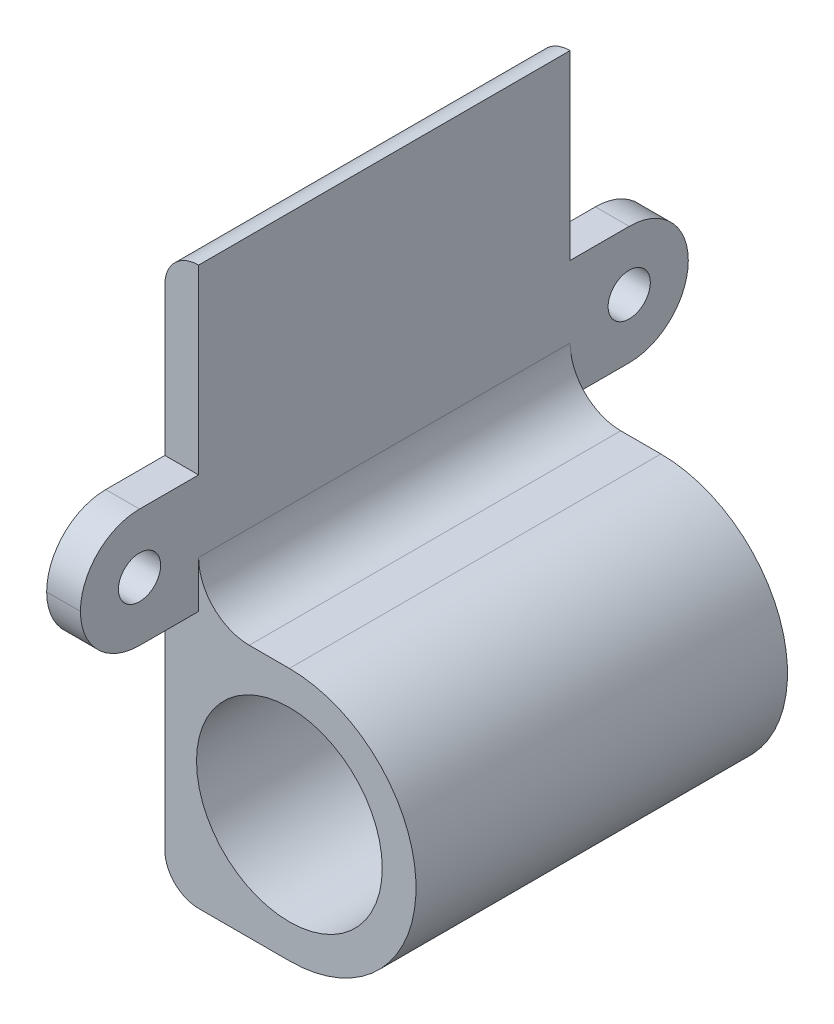
SolidWorks part; units mm, degrees
ref_plane "Front Plane" through (0, 0, 0) normal (0, 0, 1) x (1, 0, 0)
ref_plane "Top Plane" through (0, 0, 0) normal (0, 1, 0) x (1, 0, 0)
ref_plane "Right Plane" through (0, 0, 0) normal (1, 0, 0) x (0, 0, -1)
sketch "Sketch2" plane through (0, 0, 0) normal (0, 0, 1) x (1, 0, 0)
  line L0 (0, 4) -> (0, 62)
  line L3 (14.75, 0) -> (4, 0)
  line L4 (4, 66) -> (4, 36)
  line L5 (14.75, 30) -> (10, 30)
  circle A3 centre (14.75, 15) radius 11
  arc A4 (14.75, 0) -> (21.6926, 28.2966) centre (14.75, 15) ccw
  arc A5 (0, 62) -> (4, 66) centre (4, 62) cw
  arc A6 (0, 4) -> (4, 0) centre (4, 4) ccw
  arc A7 (21.6926, 28.2966) -> (14.75, 30) centre (14.75, 15) ccw
  arc A8 (4, 36) -> (10, 30) centre (10, 36) ccw
  point P16 (0, 66)
  point P19 (0, 0)
  dimension "D2" = 6
  dimension "D3" = 22
  dimension "D4" = 4
  dimension "D9" = 4
  dimension "D10" = 4
  dimension "D5" = 66
  dimension "D7" = 14.75
extrude "Boss-Extrude1" add sketch "Sketch2" along normal blind 44
sketch "Sketch3" plane through (0, 0, 0) normal (0, 0, -1) x (-1, 0, 0)
  line L3 (-4, 0) -> (-4, -14)
  line L4 (-4, -14) -> (0, -14)
  line L5 (0, -14) -> (0, 4)
  arc A2 (-4, 0) -> (0, 4) centre (-4, 4) ccw construction
  arc A3 (-4, 0) -> (0, 4) centre (-4, 4) ccw
  dimension "D2" = 14
extrude "Boss-Extrude2" [suppressed] add sketch "Sketch3" against normal blind 14
fillet "Fillet1" [suppressed] radius 7
sketch "Sketch4" [suppressed] plane through (4, 0, 0) normal (1, 0, 0) x (0, 0, -1)
  circle A0 centre (-7, -7) radius 2.5
  dimension "D1" = 5
extrude "Cut-Extrude1" [suppressed] cut sketch "Sketch4" against normal blind 14
ref_plane "Plane1" through (0, 0, 22) normal (0, 0, -1) x (-1, 0, 0)
sketch "Sketch5" plane through (0, 0, 44) normal (0, 0, 1) x (1, 0, 0)
  line L0 (0, 62) -> (0, 4) construction
  line L1 (0, 30.4737) -> (4, 30.4737)
  line L2 (0, 30.4737) -> (0, 44.4737)
  line L3 (0, 44.4737) -> (4, 44.4737)
  line L4 (4, 30.4737) -> (4, 44.4737)
  line L5 (20.203, 37.4737) -> (0, 37.4737) construction
  line L6 (20.203, 28.9737) -> (20.203, 45.9737) construction
  point P11 (0, 37.4737)
  dimension "D1" = 4
  dimension "D2" = 14
extrude "Boss-Extrude3" add sketch "Sketch5" along normal blind 14
fillet "Fillet3" radius 7 2 edges at (2, 30.4737, 58) (2, 44.4737, 58)
sketch "Sketch6" plane through (4, 0, 0) normal (1, 0, 0) x (0, 0, -1)
  circle A0 centre (-51, 37.4737) radius 2.5
  dimension "D1" = 5
extrude "Cut-Extrude2" cut sketch "Sketch6" against normal blind 14
mirror "Mirror2" about plane through (0, 0, 22) normal (0, 0, -1) of "Cut-Extrude2", "Fillet3", "Boss-Extrude3"
